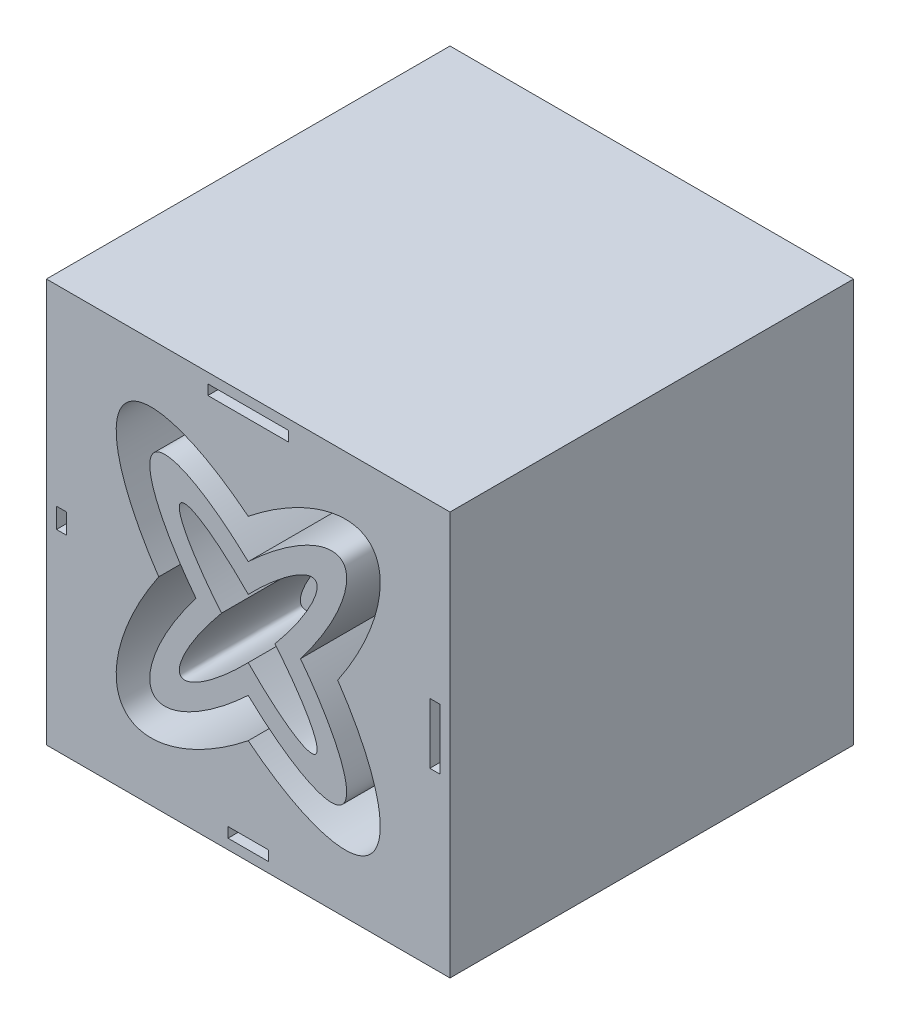
SolidWorks part; units mm, degrees
ref_plane "Plan de face" through (0, 0, 0) normal (0, 0, 1) x (1, 0, 0)
ref_plane "Plan de dessus" through (0, 0, 0) normal (0, 1, 0) x (1, 0, 0)
ref_plane "Plan de droite" through (0, 0, 0) normal (1, 0, 0) x (0, 0, -1)
sketch "Esquisse1" plane through (0, 0, 0) normal (0, 0, 1) x (1, 0, 0)
  line L1 (-100, 100) -> (100, 100)
  line L2 (-100, 100) -> (-100, -100)
  line L3 (-100, -100) -> (100, -100)
  line L4 (100, 100) -> (100, -100)
  point P4 (0, 100)
  point P6 (-100, 0)
  dimension "D1" = 200
  dimension "D2" = 200
extrude "Boss.-Extru.1" add sketch "Esquisse1" along normal blind 100 and the other way blind 100
sketch "Esquisse2" plane through (0, 0, 100) normal (0, 0, 1) x (1, 0, 0)
  line L0 (-100, -100) -> (100, -100) construction
  line L1 (10, -95) -> (-10, -95)
  line L2 (10, -95) -> (10, -90)
  line L3 (10, -90) -> (-10, -90)
  line L4 (-10, -95) -> (-10, -90)
  line L5 (95, -15) -> (90, -15)
  line L6 (95, -15) -> (95, 15)
  line L7 (95, 15) -> (90, 15)
  line L8 (90, -15) -> (90, 15)
  line L9 (-20, 95) -> (20, 95)
  line L10 (-20, 95) -> (-20, 90)
  line L11 (-20, 90) -> (20, 90)
  line L12 (20, 95) -> (20, 90)
  line L13 (-95, 5) -> (-90, 5)
  line L14 (-95, 5) -> (-95, -5)
  line L15 (-95, -5) -> (-90, -5)
  line L16 (-90, 5) -> (-90, -5)
  line L17 (100, -100) -> (100, 100) construction
  line L18 (100, 100) -> (-100, 100) construction
  line L19 (-100, 100) -> (-100, -100) construction
  ellipse E0 centre (0, 0) end of major axis (60, 67.082) minor radius 35
  ellipse E1 centre (0, 0) end of major axis (60, -67.082) minor radius 35
  ellipse E2 centre (0, 0) end of major axis (46.4018, -52.4162) minor radius 20.0006
  ellipse E3 centre (0, 0) end of major axis (46.4444, 52.3767) minor radius 20.0004
  ellipse E4 centre (0, 0) end of major axis (-33.3376, 37.2726) minor radius 10.0009
  ellipse E5 centre (0, 0) end of major axis (-33.3328, -37.2742) minor radius 10.0006
  point P50 (0, -95)
  point P53 (0, -100)
  point P54 (95, 0)
  point P57 (100, 0)
  point P58 (0, 95)
  point P61 (0, 100)
  point P62 (-95, 0)
  point P65 (-100, 0)
  dimension "D1" = 70
  dimension "D2" = 180
  dimension "D3" = 180
  dimension "D4" = 70
  dimension "D5" = 40
  dimension "D6" = 40
  dimension "D7" = 20
  dimension "D8" = 20
  dimension "D9" = 15
  dimension "D10" = 15
  dimension "D11" = 20
  dimension "D12" = 10
  dimension "D13" = 20
  dimension "D14" = 10
  dimension "D15" = 0
  dimension "D16" = 20
  dimension "D17" = 5
  dimension "D18" = 5
  dimension "D19" = 0
  dimension "D20" = 30
  dimension "D21" = 5
  dimension "D22" = 5
  dimension "D23" = 0
  dimension "D24" = 5
  dimension "D25" = 5
  dimension "D26" = 40
  dimension "D27" = 0
  dimension "D28" = 10
  dimension "D29" = 5
  dimension "D30" = 5
extrude "Enlèv. mat.-Extru.2" cut sketch "Esquisse2" against normal blind 60 contours E3 E1 E0 | E3 E2 E0 E1 | E2 E0 E1 | E3 E1 E0 E2 | E3 E1 E0 | E3 E2 E0 E1 | E2 E0 E1 | E3 E1 E0 E2 | E1 E5 E2 | E1 E5 | E2 E5 E4 | E4 E5 | E4 E5 E2 | E2 E5 E1 | E1 E5 | E0 E4 | E3 E4 E0 | E5 E4 E3 | E5 E4 E3 | E0 E4 E3 | E0 E4 | L16 L13 L14 L15 | L12 L9 L10 L11 | L4 L1 L2 L3 | L8 L7 L6 L5 region at (0, -92.5, 100) region at (0, 92.5, 100) region at (-92.5, 0, 100) region at (60.4857, 32.6846, 100) region at (0.009, 38.5656, 100) region at (-6.3268, 44.1485, 100) region at (60.4857, -32.6846, 100) region at (35.1932, -0.0087, 100) region at (-40.5543, -7.0539, 100) region at (-35.1932, 0.0087, 100) region at (-18.2859, 20.2526, 100) region at (-27.5588, 30.5763, 100) region at (27.5556, 30.5783, 100) region at (18.286, 20.2539, 100) region at (-0.009, -38.5656, 100) region at (27.5588, -30.5763, 100) region at (18.2859, -20.2526, 100) region at (-10.0272, 11.1117, 100) region at (10.0254, 11.1151, 100) region at (-18.286, -20.2539, 100) region at (-27.5556, -30.5783, 100) region at (10.0272, -11.1117, 100) region at (0, 0, 100) region at (-10.0254, -11.1151, 100)
mirror "Symétrie2" about plane through (0, 0, 0) normal (0, 0, 1) of "Enlèv. mat.-Extru.2"
scale "Echelle1" scale about centroid uniform scaling yes scale factor 0.001
